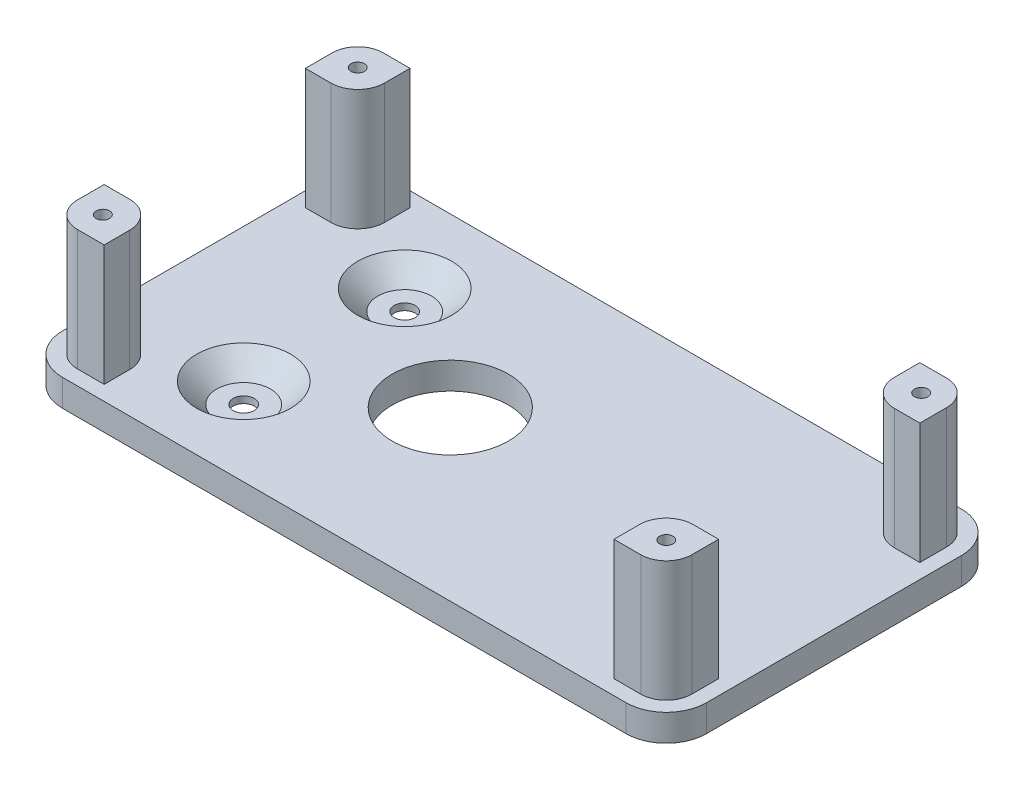
SolidWorks part; units mm, degrees
ref_plane "Front Plane" through (0, 0, 0) normal (0, 0, 1) x (1, 0, 0)
ref_plane "Top Plane" through (0, 0, 0) normal (0, 1, 0) x (1, 0, 0)
ref_plane "Right Plane" through (0, 0, 0) normal (1, 0, 0) x (0, 0, -1)
sketch "Sketch1" plane through (0, 0, 0) normal (0, 1, 0) x (1, 0, 0)
  line L1 (0, 0) -> (121.92, 0)
  line L2 (0, 0) -> (0, 63.5)
  line L3 (0, 63.5) -> (121.92, 63.5)
  line L4 (121.92, 0) -> (121.92, 63.5)
  dimension "D1" = 63.5
  dimension "D2" = 121.92
extrude "Boss-Extrude1" add sketch "Sketch1" along normal blind 5.08
fillet "Fillet1" radius 7.62 4 edges at (0, 2.54, 0) (0, 2.54, -63.5) (121.92, 2.54, -63.5) (121.92, 2.54, 0)
sketch "Sketch2" plane through (0, 5.08, 0) normal (0, 1, 0) x (1, 0, 0)
  line L0 (0, 55.88) -> (0, 7.62) construction
  line L1 (2.794, 60.706) -> (12.7, 60.706)
  line L2 (2.794, 60.706) -> (2.794, 50.8)
  line L3 (2.794, 50.8) -> (12.7, 50.8)
  line L4 (12.7, 60.706) -> (12.7, 50.8)
  line L5 (114.3, 63.5) -> (7.62, 63.5) construction
  line L6 (60.96, 63.5) -> (60.96, 0) construction
  line L7 (7.62, 0) -> (114.3, 0) construction
  line L8 (121.92, 31.75) -> (0, 31.75) construction
  line L9 (121.92, 7.62) -> (121.92, 55.88) construction
  line L10 (109.22, 60.706) -> (109.22, 50.8)
  line L11 (119.126, 50.8) -> (109.22, 50.8)
  line L12 (119.126, 60.706) -> (119.126, 50.8)
  line L13 (119.126, 60.706) -> (109.22, 60.706)
  line L14 (119.126, 2.794) -> (109.22, 2.794)
  line L15 (119.126, 2.794) -> (119.126, 12.7)
  line L16 (119.126, 12.7) -> (109.22, 12.7)
  line L17 (109.22, 2.794) -> (109.22, 12.7)
  line L18 (12.7, 2.794) -> (12.7, 12.7)
  line L19 (2.794, 12.7) -> (12.7, 12.7)
  line L20 (2.794, 2.794) -> (2.794, 12.7)
  line L21 (2.794, 2.794) -> (12.7, 2.794)
  dimension "D1" = 2.794
  dimension "D2" = 2.794
  dimension "D3" = 9.906
  dimension "D4" = 9.906
extrude "Boss-Extrude2" add sketch "Sketch2" along normal blind 22.86
fillet "Fillet2" radius 4.826 4 edges at (2.794, 16.51, -60.706) (119.126, 16.51, -60.706) (119.126, 16.51, -2.794) (2.794, 16.51, -2.794)
fillet "Fillet3" radius 5.08 4 edges at (12.7, 16.51, -12.7) (109.22, 16.51, -12.7) (109.22, 16.51, -50.8) (12.7, 16.51, -50.8)
sketch "Sketch3" plane through (0, 27.94, 0) normal (0, 1, 0) x (1, 0, 0)
  circle A0 centre (7.62, 55.88) radius 1.27
  circle A1 centre (114.3, 55.88) radius 1.27
  circle A2 centre (114.3, 7.62) radius 1.27
  circle A3 centre (7.62, 7.62) radius 1.27
  dimension "D1" = 2.54
  dimension "D2" = 2.54
  dimension "D3" = 2.54
  dimension "D4" = 2.54
extrude "Cut-Extrude1" cut sketch "Sketch3" against normal blind 22.86
sketch "Sketch5" plane through (0, 0, 0) normal (0, -1, 0) x (1, 0, 0)
  circle A0 centre (49.276, -31.75) radius 10.9982
  dimension "D1" = 24.13
  dimension "D2" = 21.9964
  dimension "D3" = 49.276
extrude "Cut-Extrude2" cut sketch "Sketch5" against normal up to next
sketch "Sketch6" plane through (0, 0, 0) normal (0, -1, 0) x (1, 0, 0)
  line L0 (0, -55.88) -> (0, -7.62) construction
  circle A0 centre (25.4, -16.51) radius 1.9939
  circle A1 centre (25.4, -46.99) radius 1.9939
  point P6 (0, -31.75)
  dimension "D1" = 3.9878
  dimension "D2" = 3.9878
  dimension "D3" = 25.4
  dimension "D4" = 15.24
  dimension "D5" = 15.24
extrude "Cut-Extrude3" cut sketch "Sketch6" against normal up to next
sketch "Sketch7" plane through (0, 5.08, 0) normal (0, 1, 0) x (1, 0, 0)
  circle A0 centre (25.4, 46.99) radius 5.08
  circle A1 centre (25.4, 16.51) radius 5.08
  dimension "D1" = 10.16
  dimension "D2" = 10.16
extrude "Cut-Extrude4" cut sketch "Sketch7" against normal blind 3.81
chamfer "Chamfer1" distance 3.81 angle 45 2 edges at (25.4, 5.08, -11.43) (25.4, 5.08, -41.91)
